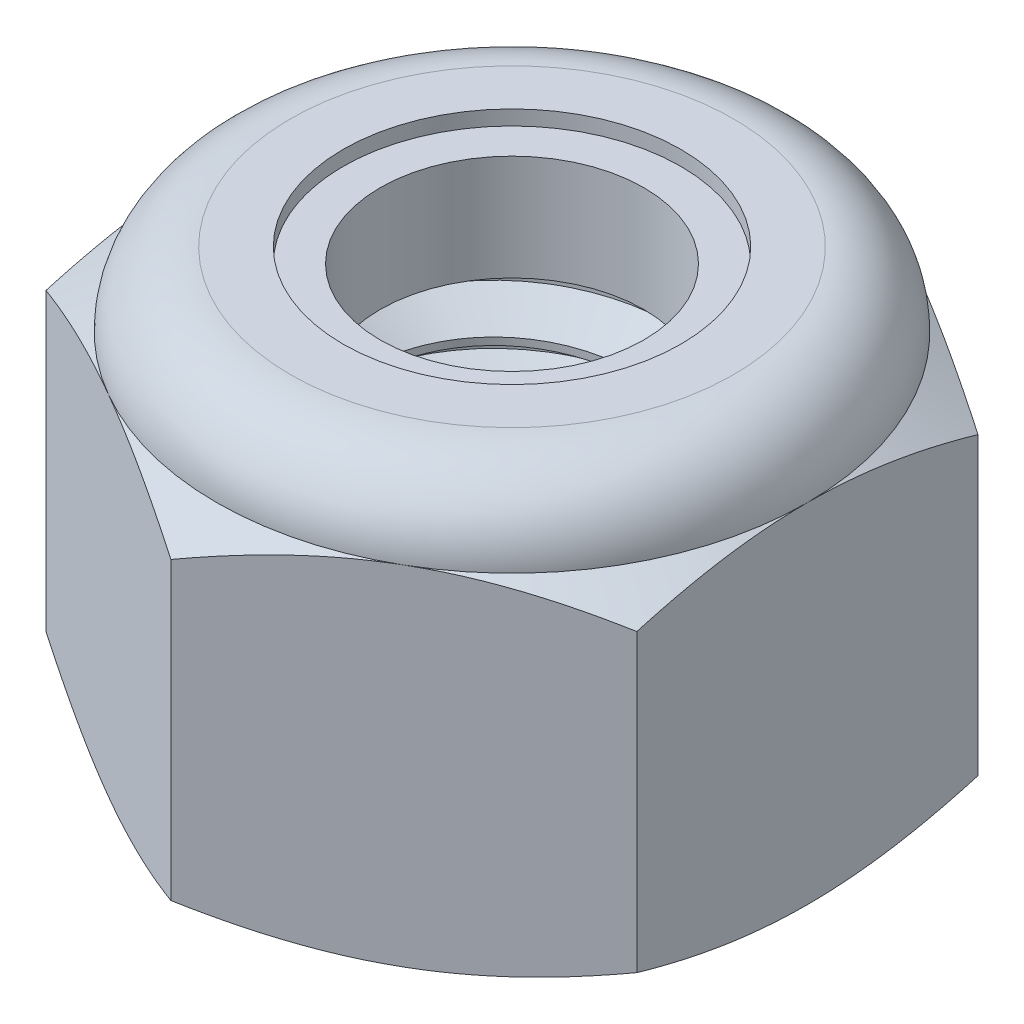
SolidWorks part; units mm, degrees
ref_plane "Front" through (0, 0, 0) normal (0, 0, 1) x (1, 0, 0)
ref_plane "Top" through (0, 0, 0) normal (0, 1, 0) x (1, 0, 0)
ref_plane "Right" through (0, 0, 0) normal (1, 0, 0) x (0, 0, -1)
sketch "Sketch1" plane through (0, 0, 0) normal (0, 1, 0) x (1, 0, 0)
  line L1 (0, 4.0415) -> (-3.5, 2.0207) construction
  line L2 (-3.5, 2.0207) -> (-3.5, -2.0207) construction
  line L3 (-3.5, -2.0207) -> (0, -4.0415) construction
  line L4 (0, -4.0415) -> (3.5, -2.0207) construction
  line L5 (3.5, -2.0207) -> (3.5, 2.0207) construction
  line L6 (3.5, 2.0207) -> (0, 4.0415) construction
  circle A0 centre (0, 0) radius 3.5 construction
  circle A1 centre (0, 0) radius 2 construction
  point P11 (0, -2)
  point P12 (0, 0)
  dimension "Thread Dia" = 4
  dimension "Width" = 7
sketch "Sketch2" plane through (0, 0, 0) normal (1, 0, 0) x (0, 0, -1)
  line L0 (-2, -2.5) -> (-2, 2.5) construction
  line L1 (0, 0) -> (0, 2.5) construction
  line L2 (0, 2.5) -> (-2, 2.5) construction
  line L3 (-2.0758, -2.4563) -> (-1.4696, -2.8063) construction
  line L4 (-1.4696, -2.8063) -> (-2.0758, -3.1563) construction
  line L5 (-2.0758, -3.1563) -> (-2.0758, -2.4563) construction
  line L6 (-1.5453, -2.7625) -> (-1.5453, -2.85) construction
  line L7 (-2.0379, -2.8063) -> (-2.0379, -2.4781) construction
  line L8 (-2, -2.5) -> (-2, -3.1125) construction
  line L9 (-2.0758, -2.8063) -> (-2, -2.8062) construction
  line L10 (-1.5453, -2.8063) -> (-1.4696, -2.8063) construction
  line L11 (-2.0379, -2.8063) -> (-2.0379, -3.1344) construction
  line L12 (-1.5625, 1.075) -> (-1.5625, 2.325) construction
  line L13 (-1.5625, 2.325) -> (-2, 2.325) construction
  line L14 (-2, 2.325) -> (-2, 1.075) construction
  line L15 (-2, 1.075) -> (-1.5625, 1.075) construction
  point P6 (-2, 0)
  point P25 (-1.5625, 2.325)
  dimension "Height" = 5
  dimension "Pitch" = 0.7
  dimension "D2" = 0.0875
  dimension "D1" = 0.4375
  dimension "D3" = 1.25
  dimension "D4" = 0.175
sketch "Sketch3" plane through (0, 0, 0) normal (0, 1, 0) x (1, 0, 0)
  line L0 (0, 4.0415) -> (3.5, 2.0207)
  line L1 (3.5, 2.0207) -> (3.5, -2.0207)
  line L2 (3.5, -2.0207) -> (0, -4.0415)
  line L3 (0, -4.0415) -> (-3.5, -2.0207)
  line L4 (-3.5, -2.0207) -> (-3.5, 2.0207)
  line L5 (-3.5, 2.0207) -> (0, 4.0415)
sketch "Sketch7" plane through (0, 0, 0) normal (0, 1, 0) x (1, 0, 0)
  circle A0 centre (0, 0) radius 3.5 construction
  circle A1 centre (0, 0) radius 3.5
extrude "Boss-Extrude2" add sketch "Sketch3" along normal up to vertex (-2.5 mm away) and the other way up to vertex (2.5 mm away) up to point (0, -2.5, 2) other way up to point (0, -2.5, 2)
sketch "Sketch4" plane through (0, 0, 0) normal (0, 1, 0) x (1, 0, 0)
  circle A0 centre (0, 0) radius 2
  circle A1 centre (0, 0) radius 2 construction
extrude "Cut-Extrude4" cut sketch "Sketch4" along normal through all both and the other way through all
sketch "Sketch6" plane through (0, 0, 0) normal (1, 0, 0) x (0, 0, -1)
  line L0 (3.5, -2.5) -> (3.5, 2.5) construction
  line L7 (3.5, 2.5) -> (3.5, 1.625) construction
  line L8 (3.5, 2.5) -> (2.625, 2.5) construction
  line L11 (3.5, 1.625) -> (4.0415, 1.625)
  line L13 (4.0415, 1.625) -> (4.0415, 2.5)
  line L14 (4.0415, 2.5) -> (2.625, 2.5)
  arc A1 (3.5, 1.625) -> (2.625, 2.5) centre (2.625, 1.625) ccw
  point P15 (3.5, 0)
  dimension "D1" = 0.875
revolve "Cut-Revolve1" cut sketch "Sketch6" angle 360 about axis through (0, 2.5, 0) along (0, -1, 0)
extrude "Cut-Extrude5" cut sketch "Sketch7" against normal through all draft 60 from surface flip side to cut starting at face at (0, 1.625, -3.5242)
sketch "Sketch19" plane through (0, -2.5, 0) normal (0, -1, 0) x (1, 0, 0)
  circle A0 centre (0, 0) radius 3.5 construction
  circle A1 centre (0, 0) radius 3.5
extrude "Cut-Extrude6" cut sketch "Sketch19" against normal through all draft 60 flip side to cut
chamfer "Chamfer1" distance 0.2625 angle 45 1 edges at (0, -2.5, 2)
sketch "Sketch24" plane through (0, 0, 0) normal (1, 0, 0) x (0, 0, -1)
  line L0 (-2, 2.325) -> (-1.5625, 2.325)
  line L1 (-1.5625, 2.325) -> (-1.5625, 1.075)
  line L2 (-1.5625, 1.075) -> (-2, 1.075)
  line L3 (-2, 1.075) -> (-2, 2.325)
revolve "Revolve1" add sketch "Sketch24" angle 360 about L1
ref_plane "Contact Plane 1" through (0, 2.5, 0) normal (0, 1, 0) x (1, 0, 0)
ref_plane "Contact Plane 2" through (0, -2.5, 0) normal (0, -1, 0) x (-1, 0, 0)
sketch "Sketch5" plane through (0, -2.5, 0) normal (0, 1, 0) x (1, 0, 0)
  circle A1 centre (0, 0) radius 2
  circle A2 centre (0, 0) radius 2 construction
curve "Helix/Spiral1" pitch 0.7 height 5 radius 2 centre (0, -2.5, 0) axis (0, 1, 0) start towards (0, 0, 1)
sketch "Sketch21" plane through (0, 0, 0) normal (1, 0, 0) x (0, 0, -1)
  line L0 (-2.0379, -2.4781) -> (-2.0379, -3.1344)
  line L1 (-2.0379, -3.1344) -> (-1.5453, -2.85)
  line L2 (-1.5453, -2.85) -> (-1.5453, -2.7625)
  line L3 (-1.5453, -2.7625) -> (-2.0379, -2.4781)
sweep "Sweep1" add profiles "Sketch21" path "Helix/Spiral1"
sketch "Sketch23" plane through (0, 1.075, 0) normal (0, 1, 0) x (1, 0, 0)
  line L0 (0, 0) -> (0, -2) construction
  circle A1 centre (0, 0) radius 2.0758
extrude "Cut-Extrude8" cut sketch "Sketch23" along normal through all and the other way through all draft 45
combine bodies "Combine1" operation type add bodies to combine 147 143
sketch "Sketch30" plane through (0, -2.5, 0) normal (0, -1, 0) x (1, 0, 0)
  circle A0 centre (0, 0) radius 2.2625 construction
  circle A1 centre (0, 0) radius 2.2625
extrude "Cut-Extrude12" cut sketch "Sketch30" along normal through all and the other way through all draft 45
equation "\"D2@Sketch2\" = \"Pitch@Sketch2\" / 8"
equation "\"D1@Sketch2\"=\"Pitch@Sketch2\"*.625"
equation "\"D3@Sketch2\"=\"Height@Sketch2\"/4"
equation "\"D4@Sketch2\"=\"Pitch@Sketch2\"/4"
equation "\"D4@Helix/Spiral1\"=\"Pitch@Sketch2\""
equation "\"D3@Helix/Spiral1\"=\"Height@Sketch2\""
equation "\"D1@Sketch6\"=\"Pitch@Sketch2\"*1.25"
equation "\"D1@Chamfer1\"=\"Pitch@Sketch2\"*.375"
